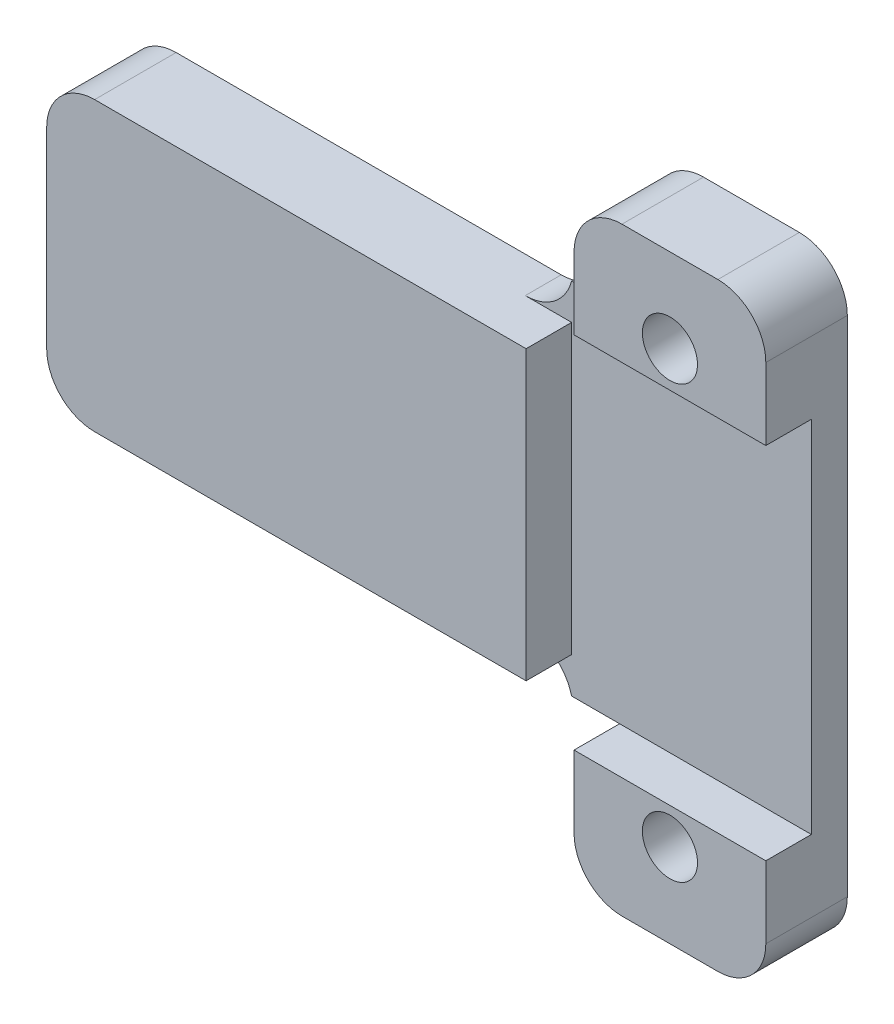
SolidWorks part; units mm, degrees
ref_plane "Płaszczyzna przednia" through (0, 0, 0) normal (0, 0, 1) x (1, 0, 0)
ref_plane "Płaszczyzna górna" through (0, 0, 0) normal (0, 1, 0) x (1, 0, 0)
ref_plane "Płaszczyzna prawa" through (0, 0, 0) normal (1, 0, 0) x (0, 0, -1)
sketch "Szkic1" plane through (0, 0, 0) normal (0, 0, 1) x (1, 0, 0)
  line L0 (0, 0) -> (0, 6)
  line L1 (0, 0) -> (0, -6)
  line L2 (0, 6) -> (20, 6)
  line L3 (0, -6) -> (20, -6)
  line L4 (20, 6) -> (20, -6)
  dimension "D1" = 6
  dimension "D2" = 6
  dimension "D3" = 20
  dimension "D4" = 20
extrude "Dodanie-wyciągnięcie1" add sketch "Szkic1" along normal blind 3.4
sketch "Szkic3" plane through (0, 0, 0) normal (0, 0, 1) x (1, 0, 0)
  line L0 (20, 6) -> (20, 7.5)
  line L1 (20, 7.5) -> (30, 7.5)
  line L2 (30, 7.5) -> (30, -7.5)
  line L3 (30, -7.5) -> (20, -7.5)
  line L4 (20, -7.5) -> (20, -6)
  line L5 (20, 6) -> (20, -6)
  dimension "D1" = 1.5
  dimension "D2" = 15
  dimension "D3" = 10
extrude "Dodanie-wyciągnięcie2" add sketch "Szkic3" along normal blind 1.5
fillet "Zaokrąglenie1" radius 2 4 edges at (20, -6, 0.75) (20, 6, 0.75) (0, -6, 1.7) (0, 6, 1.7)
sketch "Szkic4" plane through (0, 0, 0) normal (0, 0, 1) x (1, 0, 0)
  line L0 (22, 7.5) -> (22, 12.5)
  line L1 (30, 7.5) -> (20, 7.5) construction
  line L2 (22, 12.5) -> (30, 12.5)
  line L3 (30, 12.5) -> (30, 7.5)
  line L4 (20, 6) -> (20, -6) construction
  line L5 (22, 7.5) -> (30, 7.5)
  line L6 (55, 0) -> (-55, 0) construction
  line L7 (22, -7.5) -> (22, -12.5)
  line L8 (22, -12.5) -> (30, -12.5)
  line L9 (30, -12.5) -> (30, -7.5)
  line L10 (22, -7.5) -> (30, -7.5)
  dimension "D1" = 2
  dimension "D2" = 5
extrude "Dodanie-wyciągnięcie3" add sketch "Szkic4" along normal blind 3.4
fillet "Zaokrąglenie2" radius 2 4 edges at (30, 12.5, 1.7) (22, 12.5, 1.7) (30, -12.5, 1.7) (22, -12.5, 1.7)
sketch "Szkic6" plane through (0, 0, 0) normal (0, 0, 1) x (1, 0, 0)
  line L0 (30, -7.5) -> (30, 7.5) construction
  line L1 (20, 6) -> (2, 6) construction
  circle A0 centre (26, 9) radius 1.15
  circle A1 centre (26, -9) radius 1.15
  point P4 (0, 0)
  point P5 (0, 0)
  point P8 (30, -9.0331)
  dimension "D1" = 2.3
  dimension "D2" = 2.3
  dimension "D4" = 4
  dimension "D5" = 3
  dimension "D3" = 18
extrude "Wytnij-wyciągnięcie1" cut sketch "Szkic6" along normal blind 3.5
